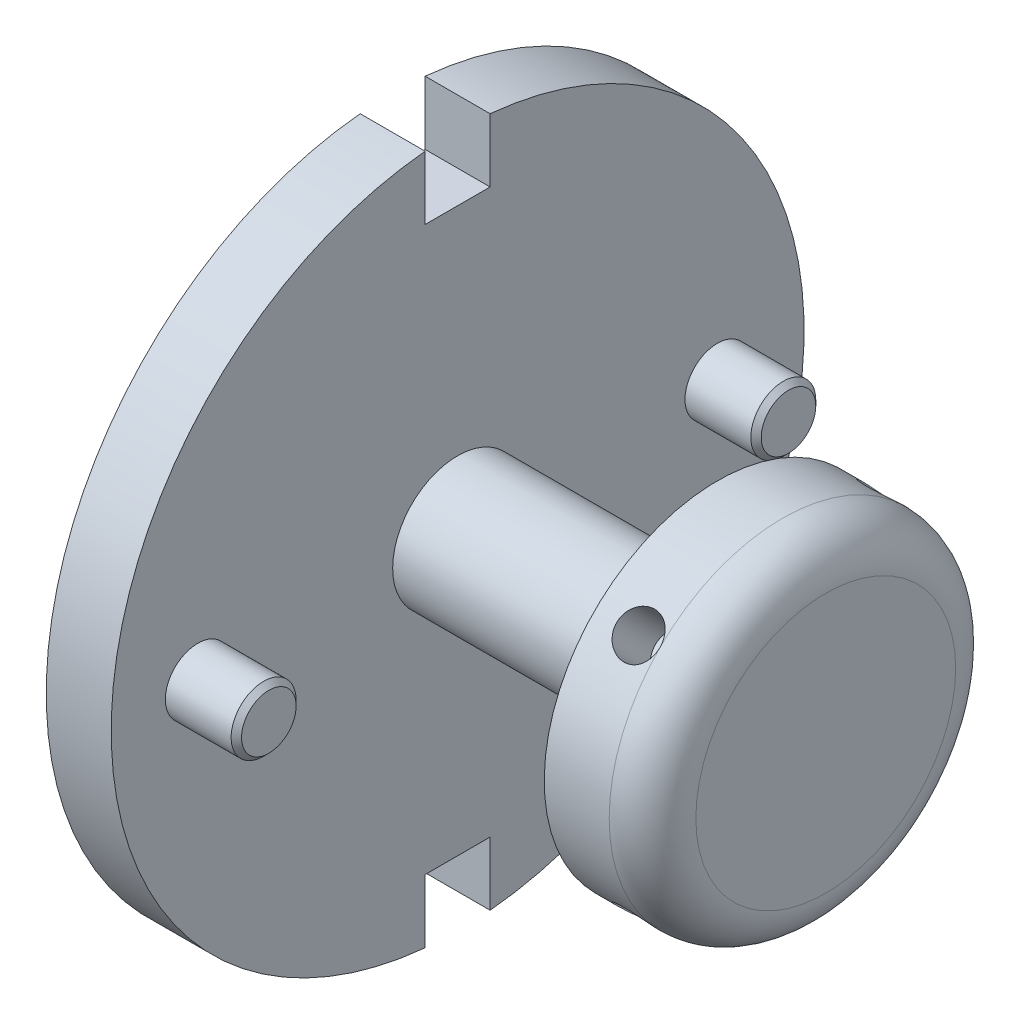
SolidWorks part; units mm, degrees
ref_plane "Front Plane" through (0, 0, 0) normal (1, 0, 0) x (0, 1, 0)
ref_plane "Top Plane" through (0, 0, 0) normal (0, 0, 1) x (0, 1, 0)
ref_plane "Right Plane" through (0, 0, 0) normal (0, 1, 0) x (-1, 0, 0)
sketch "Sketch1" plane through (0, 0, 0) normal (1, 0, 0) x (0, 1, 0)
  line L0 (0, 101.6) -> (0, 0) construction
  line L1 (0, 0) -> (101.6, 0) construction
  line L2 (101.1525, -9.525) -> (82.55, -9.525)
  line L3 (82.55, -9.525) -> (82.55, 9.525)
  line L4 (101.1525, 9.525) -> (82.55, 9.525)
  line L5 (-101.1525, -9.525) -> (-82.55, -9.525)
  line L6 (-82.55, -9.525) -> (-82.55, 9.525)
  line L7 (-101.1525, 9.525) -> (-82.55, 9.525)
  circle A0 centre (0, 0) radius 101.6
  circle A1 centre (0, 0) radius 19.05
  circle A2 centre (0, 0) radius 25.4
  circle A3 centre (0, 0) radius 50.8
  circle A4 centre (0, 0) radius 76.2 construction
  circle A5 centre (0, 76.2) radius 9.525
  point P8 (0, 76.2)
  point P16 (82.55, 0)
  dimension "D1" = 38.1
  dimension "D2" = 50.8
  dimension "D3" = 101.6
  dimension "D4" = 203.2
  dimension "D5" = 152.4
  dimension "D6" = 19.05
  dimension "D7" = 82.55
  dimension "D8" = 9.525
extrude "Boss-Extrude1" add sketch "Sketch1" against normal blind 19.05 contours L4 A0 L2 L3 A5 A3 | A5 | A3 A2 | A1 | A2 A1 region at (0, 0, -98.7326) region at (0, 0, 0) region at (0, -24.6816, 0) region at (0, -49.3632, 0) region at (0, 0, 76.2)
extrude "Boss-Extrude2" add sketch "Sketch1<3>" along normal blind 20.828 contours A5 region at (0, 0, 76.2)
sketch "Sketch1<3>" plane through (0, 0, 0) normal (1, 0, 0) x (0, 1, 0) same geometry as "Sketch1"
chamfer "Chamfer1" distance 1.524 angle 45 1 edges at (20.828, 0, 66.675)
extrude "Boss-Extrude3" add sketch "Sketch1<4>" against normal blind 44.45 from surface contours A1 region at (0, 0, 0) starting at face at (-19.05, 0, 0)
sketch "Sketch1<4>" plane through (0, 0, 0) normal (1, 0, 0) x (0, 1, 0) same geometry as "Sketch1"
ref_plane "Plane1" through (-38.1, 0, 0) normal (-1, 0, 0) x (0, 0, 1)
extrude "Boss-Extrude4" add sketch "Sketch1<6>" along normal up to surface (-19.05 mm away) from surface contours A2 A1 region at (0, -24.6816, 0) up to face at (-19.05, 0, -19.05) starting at plane "Plane1"
sketch "Sketch1<6>" plane through (0, 0, 0) normal (1, 0, 0) x (0, 1, 0) same geometry as "Sketch1"
extrude "Boss-Extrude5" add sketch "Sketch1<7>" along normal blind 76.2 contours A1 region at (0, 0, 0)
sketch "Sketch1<7>" plane through (0, 0, 0) normal (1, 0, 0) x (0, 1, 0) same geometry as "Sketch1"
extrude "Boss-Extrude6" add sketch "Sketch1<8>" along normal blind 31.75 from surface contours A3 A2 | A2 A1 | A1 region at (0, 0, 0) region at (0, -24.6816, 0) region at (0, -49.3632, 0) starting at face at (76.2, 0, -19.05)
sketch "Sketch1<8>" plane through (0, 0, 0) normal (1, 0, 0) x (0, 1, 0) same geometry as "Sketch1"
ref_axis "Axis1" through (107.95, 0, 0) along (-1, 0, 0)
pattern_circular "CirPattern2" count 2 over 360 about axis through (107.95, 0, 0) along (-1, 0, 0) of "Boss-Extrude2", "Chamfer1"
fillet "Fillet1" radius 12.7 1 edges at (107.95, 0, -50.8)
ref_plane "Plane4" through (88.9, 0, 0) normal (-1, 0, 0) x (0, 0, 1)
sketch "Sketch2" plane through (88.9, 0, 0) normal (-1, 0, 0) x (0, 0, 1)
  line L0 (0, 0) -> (-87.4455, 87.4455)
  line L1 (0, 0) -> (-124.6446, 0) construction
  line L2 (-31.1492, 40.1294) -> (-20.1158, 29.096)
  line L3 (-20.1158, 29.096) -> (-24.6059, 24.6059)
  line L4 (-31.1492, 40.1294) -> (-63.2072, 72.1875)
  line L5 (-63.2072, 72.1875) -> (-67.6974, 67.6974)
  circle A0 centre (0, 0) radius 50.8 construction
  circle A1 centre (0, 0) radius 50.8
  point P7 (-35.921, 35.921)
  dimension "D1" = 45
  dimension "D2" = 16.002
  dimension "D3" = 6.35
revolve "Cut-Revolve1" cut sketch "Sketch2" angle 360 about L0 region at (88.9, 32.4526, -27.9812) region at (88.9, 54.0106, -49.5138)
pattern_circular "CirPattern3" count 4 over 360 about axis through (107.95, 0, 0) along (-1, 0, 0) of "Cut-Revolve1"
